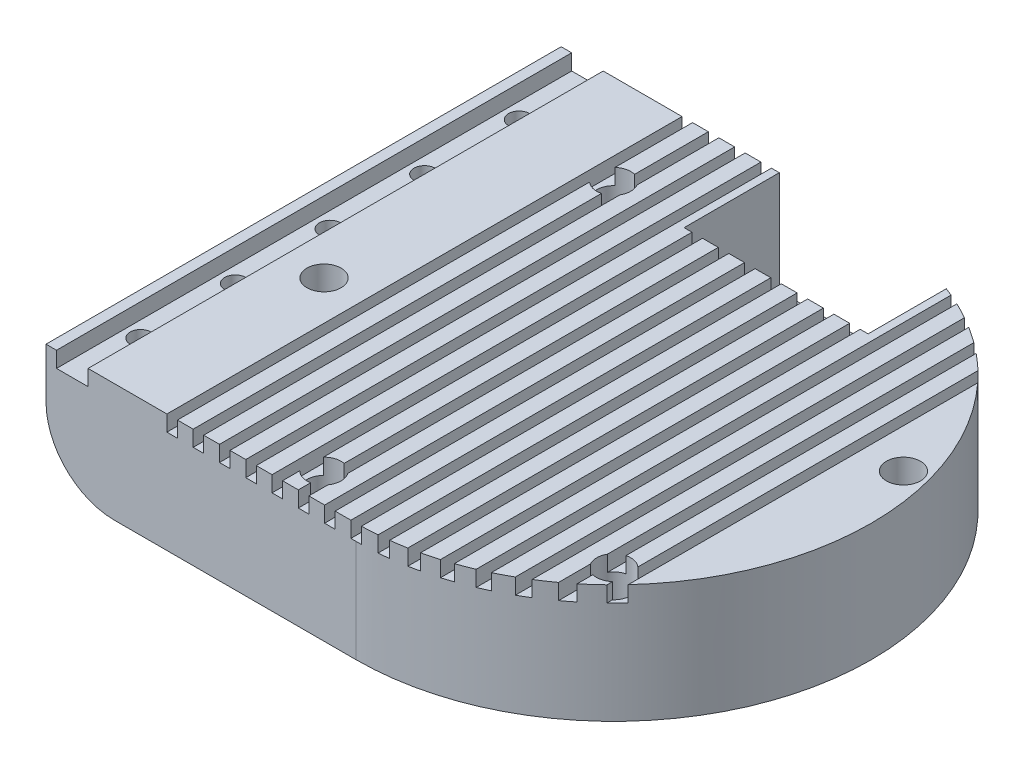
SolidWorks part; units mm, degrees
material "6061 합금"
ref_plane "정면" through (0, 0, 0) normal (0, 0, 1) x (1, 0, 0)
ref_plane "윗면" through (0, 0, 0) normal (0, 1, 0) x (1, 0, 0)
ref_plane "우측면" through (0, 0, 0) normal (1, 0, 0) x (0, 0, -1)
sketch "스케치1" plane through (0, 0, 0) normal (0, 1, 0) x (1, 0, 0)
  line L0 (-59, 45) -> (-59, -45)
  line L3 (11.6469, 43.4667) -> (0, 0) construction
  line L4 (0, 0) -> (0, 49) construction
  line L5 (0, 49) -> (-59, 49)
  line L6 (-59, 49) -> (-59, 45)
  line L7 (0, -49) -> (-59, -49)
  line L8 (-59, -49) -> (-59, -45)
  circle A1 centre (0, 0) radius 35.5
  circle A4 centre (0, 0) radius 45
  circle A5 centre (11.6469, 43.4667) radius 2
  circle A6 centre (43.4667, 11.6469) radius 2
  circle A7 centre (31.8198, -31.8198) radius 2
  circle A8 centre (-11.6469, -43.4667) radius 2
  circle A9 centre (-43.4667, -11.6469) radius 2
  circle A10 centre (-31.8198, 31.8198) radius 2
  circle A11 centre (0, 0) radius 49
  point P7 (-59, 0)
  point P26 (0, 0)
  dimension "D1" = 71
  dimension "D2" = 90
  dimension "D4" = 90
  dimension "D5" = 4
  dimension "D3" = 98
  dimension "D6" = 15
  dimension "D9" = 59
  dimension "D7" = 6
extrude "보스-돌출4" add sketch "스케치1" along normal blind 22.5 contours L0 A11 | A11 A10 A4 A5 A6 A7 A8 A9 | A10 A4 A9 A8 A7 A6 A5 A1 region at (-57.8561, 0, -47) region at (33.6682, 0, -33.6682) region at (40.7606, 0, 15.8318)
extrude "보스-돌출5" add sketch "스케치1<6>" against normal blind 10 from surface contours A1 region at (0, 0, 0) starting at face at (-31.8198, 22.5, -29.8198)
sketch "스케치1<6>" plane through (0, 0, 0) normal (0, 1, 0) x (1, 0, 0) same geometry as "스케치1"
sketch "스케치10" plane through (0, 22.5, 0) normal (0, 1, 0) x (1, 0, 0)
  line L0 (-59, 49) -> (-59, -49) construction
  line L1 (-57, -49) -> (-51, -49)
  line L2 (-57, -49) -> (-57, 49)
  line L3 (-57, 49) -> (-51, 49)
  line L4 (-51, -49) -> (-51, 49)
  line L5 (-57, -49) -> (-51, 49) construction
  line L6 (-57, 49) -> (-51, -49) construction
  line L7 (0, 49) -> (-59, 49) construction
  line L8 (0, -49) -> (-59, -49) construction
  point P0 (-54, 0)
  point P7 (0, 0)
  point P11 (0, 0)
  point P12 (0, 0)
  point P15 (0, 0)
  dimension "D1" = 6
  dimension "D2" = 2
extrude "컷-돌출8" cut sketch "스케치10" against normal blind 3
sketch "스케치11" plane through (0, 22.5, 0) normal (0, 1, 0) x (1, 0, 0)
  line L0 (-31.8198, 31.8198) -> (0, 0) construction
  line L1 (0, 0) -> (11.6469, 43.4667) construction
  circle A0 centre (-31.8198, 31.8198) radius 3.25
  circle A1 centre (11.6469, 43.4667) radius 3.25
  circle A2 centre (43.4667, 11.6469) radius 3.25
  circle A3 centre (31.8198, -31.8198) radius 3.25
  circle A4 centre (-11.6469, -43.4667) radius 3.25
  circle A5 centre (-43.4667, -11.6469) radius 3.25
  point P15 (0, 0)
  dimension "D1" = 6.5
  dimension "D3" = 60
  dimension "D2" = 6
extrude "컷-돌출9" cut sketch "스케치11" against normal blind 17.5
sketch "스케치12" plane through (0, 0, 0) normal (0, -1, 0) x (1, 0, 0)
  line L0 (0, -49) -> (-59, -49) construction
  line L1 (-17.5, -49) -> (17.5, -49)
  line L2 (-17.5, -49) -> (-17.5, -30.8869)
  line L3 (-17.5, -30.8869) -> (17.5, -30.8869)
  line L4 (17.5, -49) -> (17.5, -30.8869)
  line L5 (-17.5, -49) -> (17.5, -30.8869) construction
  line L6 (-17.5, -30.8869) -> (17.5, -49) construction
  circle A3 centre (0, 0) radius 35.5 construction
  point P0 (0, -39.9434)
  point P5 (0, 0)
  point P7 (0, 0)
  point P12 (0, 0)
  point P14 (0, 0)
  dimension "D1" = 35
extrude "컷-돌출10" cut sketch "스케치12" against normal blind 30 from offset 3 offset against normal yes
sketch "스케치13" plane through (0, 19.5, 0) normal (0, 1, 0) x (1, 0, 0)
  line L0 (-54, 36) -> (-54, -36) construction
  line L1 (-51, 0) -> (-57, 0) construction
  line L2 (-51, -49) -> (-51, 49) construction
  line L3 (-57, 49) -> (-57, -49) construction
  line L4 (-54, 36) -> (-54, 18) construction
  circle A0 centre (-54, 36) radius 2
  circle A1 centre (-54, 18) radius 2
  circle A2 centre (-54, 0) radius 2
  circle A3 centre (-54, -18) radius 2
  circle A4 centre (-54, -36) radius 2
  point P2 (-54, 0)
  point P10 (-54, 0)
  dimension "D2" = 4
  dimension "D1" = 36
  dimension "D4" = 18
  dimension "D3" = 5
extrude "컷-돌출11" cut sketch "스케치13" against normal blind 30
sketch "스케치14" plane through (0, 0, 0) normal (0, -1, 0) x (1, 0, 0)
  line L0 (-54, 36) -> (-54, -36) construction
  line L1 (-54, 36) -> (-54, 18) construction
  circle A0 centre (-54, 36) radius 3.25
  circle A1 centre (-54, 18) radius 3.25
  circle A2 centre (-54, 0) radius 3.25
  circle A3 centre (-54, -18) radius 3.25
  circle A4 centre (-54, -36) radius 3.25
  dimension "D1" = 6.5
  dimension "D3" = 18
  dimension "D2" = 5
extrude "컷-돌출12" cut sketch "스케치14" against normal blind 17.5
sketch "스케치15" plane through (0, 0, 0) normal (0, 0, 1) x (1, 0, 0)
  line L1 (-1, 19.5) -> (1, 19.5)
  line L2 (-1, 19.5) -> (-1, 25.5)
  line L3 (-1, 25.5) -> (1, 25.5)
  line L4 (1, 19.5) -> (1, 25.5)
  line L5 (-1, 19.5) -> (1, 25.5) construction
  line L6 (-1, 25.5) -> (1, 19.5) construction
  line L7 (4, 25.5) -> (6, 25.5)
  line L8 (6, 19.5) -> (6, 25.5)
  line L9 (4, 19.5) -> (4, 25.5)
  line L10 (4, 19.5) -> (6, 19.5)
  line L11 (9, 25.5) -> (11, 25.5)
  line L12 (11, 19.5) -> (11, 25.5)
  line L13 (9, 19.5) -> (9, 25.5)
  line L14 (9, 19.5) -> (11, 19.5)
  line L15 (14, 25.5) -> (16, 25.5)
  line L16 (16, 19.5) -> (16, 25.5)
  line L17 (14, 19.5) -> (14, 25.5)
  line L18 (14, 19.5) -> (16, 19.5)
  line L19 (19, 25.5) -> (21, 25.5)
  line L20 (21, 19.5) -> (21, 25.5)
  line L21 (19, 19.5) -> (19, 25.5)
  line L22 (19, 19.5) -> (21, 19.5)
  line L23 (24, 25.5) -> (26, 25.5)
  line L24 (26, 19.5) -> (26, 25.5)
  line L25 (24, 19.5) -> (24, 25.5)
  line L26 (24, 19.5) -> (26, 19.5)
  line L27 (29, 25.5) -> (31, 25.5)
  line L28 (31, 19.5) -> (31, 25.5)
  line L29 (29, 19.5) -> (29, 25.5)
  line L30 (29, 19.5) -> (31, 19.5)
  line L31 (34, 25.5) -> (36, 25.5)
  line L32 (36, 19.5) -> (36, 25.5)
  line L33 (34, 19.5) -> (34, 25.5)
  line L34 (34, 19.5) -> (36, 19.5)
  line L35 (-1, 25.5) -> (4, 25.5) construction
  line L36 (-6, 25.5) -> (-4, 25.5)
  line L37 (-6, 19.5) -> (-6, 25.5)
  line L38 (-4, 19.5) -> (-4, 25.5)
  line L39 (-6, 19.5) -> (-4, 19.5)
  line L40 (-11, 25.5) -> (-9, 25.5)
  line L41 (-11, 19.5) -> (-11, 25.5)
  line L42 (-9, 19.5) -> (-9, 25.5)
  line L43 (-11, 19.5) -> (-9, 19.5)
  line L44 (-16, 25.5) -> (-14, 25.5)
  line L45 (-16, 19.5) -> (-16, 25.5)
  line L46 (-14, 19.5) -> (-14, 25.5)
  line L47 (-16, 19.5) -> (-14, 19.5)
  line L48 (-21, 25.5) -> (-19, 25.5)
  line L49 (-21, 19.5) -> (-21, 25.5)
  line L50 (-19, 19.5) -> (-19, 25.5)
  line L51 (-21, 19.5) -> (-19, 19.5)
  line L52 (-26, 25.5) -> (-24, 25.5)
  line L53 (-26, 19.5) -> (-26, 25.5)
  line L54 (-24, 19.5) -> (-24, 25.5)
  line L55 (-26, 19.5) -> (-24, 19.5)
  line L56 (-31, 25.5) -> (-29, 25.5)
  line L57 (-31, 19.5) -> (-31, 25.5)
  line L58 (-29, 19.5) -> (-29, 25.5)
  line L59 (-31, 19.5) -> (-29, 19.5)
  line L60 (-36, 25.5) -> (-34, 25.5)
  line L61 (-36, 19.5) -> (-36, 25.5)
  line L62 (-34, 19.5) -> (-34, 25.5)
  line L63 (-36, 19.5) -> (-34, 19.5)
  line L64 (-1, 25.5) -> (-6, 25.5) construction
  line L65 (49, 22.5) -> (0, 22.5) construction
  point P0 (0, 22.5)
  point P5 (0, 0)
  point P9 (0, 0)
  dimension "D1" = 2
  dimension "D2" = 3
  dimension "D4" = 5
  dimension "D6" = 5
  dimension "D3" = 8
  dimension "D5" = 8
extrude "컷-돌출13" cut sketch "스케치15" against normal mid plane 300
fillet "필렛2" radius 13 1 edges at (-59, 0, 0)
sketch "스케치17" plane through (0, 0, 0) normal (0, -1, 0) x (1, 0, 0)
  line L3 (-2.2112, 42.1921) -> (0, 0) construction
  line L4 (0, 0) -> (23.011, 35.4338) construction
  line L5 (-11.6469, 43.4667) -> (0, 0) construction
  line L6 (31.8198, 31.8198) -> (0, 0) construction
  line L7 (35.4338, 23.011) -> (0, 0) construction
  line L8 (0, 0) -> (42.1921, -2.2112) construction
  line L9 (43.4667, -11.6469) -> (0, 0) construction
  line L10 (-42.1921, 2.2112) -> (0, 0) construction
  line L11 (0, 0) -> (-35.4338, -23.011) construction
  line L12 (-31.8198, -31.8198) -> (0, 0) construction
  line L15 (0, 0) -> (11.6469, -43.4667) construction
  line L16 (24.2336, -34.6092) -> (0, 0) construction
  line L17 (0, 0) -> (37.645, -19.1811) construction
  line L18 (-43.4667, 11.6469) -> (0, 0) construction
  line L19 (-37.645, 19.1811) -> (0, 0) construction
  line L20 (0, 0) -> (-19.1811, 37.645) construction
  line L24 (-37.645, 19.1811) -> (-19.1811, 37.645) construction
  arc A5 (20.424, 31.4501) -> (-1.9626, 37.4486) centre (0, 0) ccw
  arc A6 (25.598, 39.4175) -> (-2.4598, 46.9356) centre (0, 0) ccw
  arc A7 (0, -49) -> (0, 49) centre (0, 0) ccw construction
  circle A8 centre (0, 0) radius 35.5 construction
  arc A9 (-2.4598, 46.9356) -> (-1.9626, 37.4486) centre (-2.2112, 42.1921) ccw
  arc A10 (20.424, 31.4501) -> (25.598, 39.4175) centre (23.011, 35.4338) ccw
  arc A11 (39.4175, 25.598) -> (31.4501, 20.424) centre (35.4338, 23.011) ccw
  arc A12 (37.4486, -1.9626) -> (46.9356, -2.4598) centre (42.1921, -2.2112) ccw
  arc A13 (41.8773, -21.3376) -> (33.4127, -17.0246) centre (37.645, -19.1811) ccw
  arc A14 (21.5091, -30.7182) -> (26.9581, -38.5001) centre (24.2336, -34.6092) ccw
  arc A17 (-39.4175, -25.598) -> (-31.4501, -20.424) centre (-35.4338, -23.011) ccw
  arc A18 (-37.4486, 1.9626) -> (-46.9356, 2.4598) centre (-42.1921, 2.2112) ccw
  arc A19 (46.9356, -2.4598) -> (39.4175, 25.598) centre (0, 0) ccw
  arc A20 (37.4486, -1.9626) -> (31.4501, 20.424) centre (0, 0) ccw
  arc A21 (26.9581, -38.5001) -> (41.8773, -21.3376) centre (0, 0) ccw
  arc A22 (21.5091, -30.7182) -> (33.4127, -17.0246) centre (0, 0) ccw
  arc A25 (-41.8773, 21.3376) -> (-33.4127, 17.0246) centre (-37.645, 19.1811) ccw
  arc A26 (-17.0246, 33.4127) -> (-21.3376, 41.8773) centre (-19.1811, 37.645) ccw
  arc A27 (-17.0246, 33.4127) -> (-33.4127, 17.0246) centre (0, 0) ccw
  arc A29 (-46.9356, 2.4598) -> (-39.4175, -25.598) centre (0, 0) ccw
  arc A30 (-37.4486, 1.9626) -> (-31.4501, -20.424) centre (0, 0) ccw
  arc A34 (-46.9356, 2.4598) -> (-39.4175, -25.598) centre (0, 0) ccw
  arc A35 (-21.3376, 41.8773) -> (-41.8773, 21.3376) centre (0, 0) ccw
  arc A36 (25.598, 39.4175) -> (-2.4598, 46.9356) centre (0, 0) ccw
  arc A37 (46.9356, -2.4598) -> (39.4175, 25.598) centre (0, 0) ccw
  arc A38 (26.9581, -38.5001) -> (41.8773, -21.3376) centre (0, 0) ccw
  point P4 (0, 0)
  point P6 (0, 0)
  line M10 (-46, 49) -> (-46, -49)
  dimension "D3" = 12
  dimension "D4" = 2
  dimension "D5" = 2
  dimension "D2" = 12
  dimension "D6" = 12
  dimension "D7" = 12
  dimension "D8" = 12
  dimension "D9" = 12
  dimension "D10" = 12
  dimension "D11" = 20
  dimension "D14" = 12
  dimension "D15" = 12
extrude "컷-돌출16" cut sketch "스케치17" against normal blind 18 contours A26 A35 A25 A27 | A30 A18 A29 A17 M10 | A5 A10 A6 A9 | A20 A12 A19 A11 | A22 A14 A21 A13 region at (10.678, 0, 39.8507) region at (39.8507, 0, 10.678) region at (31.4027, 0, -27.2979) region at (-39.6315, 0, -10.9866) region at (-29.1727, 0, 29.1727)
sketch "스케치18" plane through (0, 0, 0) normal (0, -1, 0) x (1, 0, 0)
  line L0 (-28, 49) -> (-59, 49)
  line L1 (-59, 49) -> (-59, 37.9473)
  line L2 (-59, -49) -> (-59, 49) construction
  line L3 (-28, -49) -> (-59, -49)
  line L4 (-59, -49) -> (-59, -37.9473)
  circle A0 centre (-28, 0) radius 49
  line M10 (-46, -9.6437) -> (-46, -49)
  line M11 (-46, -49) -> (0, -49)
  line M13 (0, 49) -> (-46, 49)
  line M14 (-46, 49) -> (-46, 5.0506)
  dimension "D1" = 28
extrude "컷-돌출17" [suppressed] cut sketch "스케치18" against normal blind 30 contours A0 L4 L3 M10 | A0 M10 M11 | A0 L0 L1 M14 | A0 M13 M14
